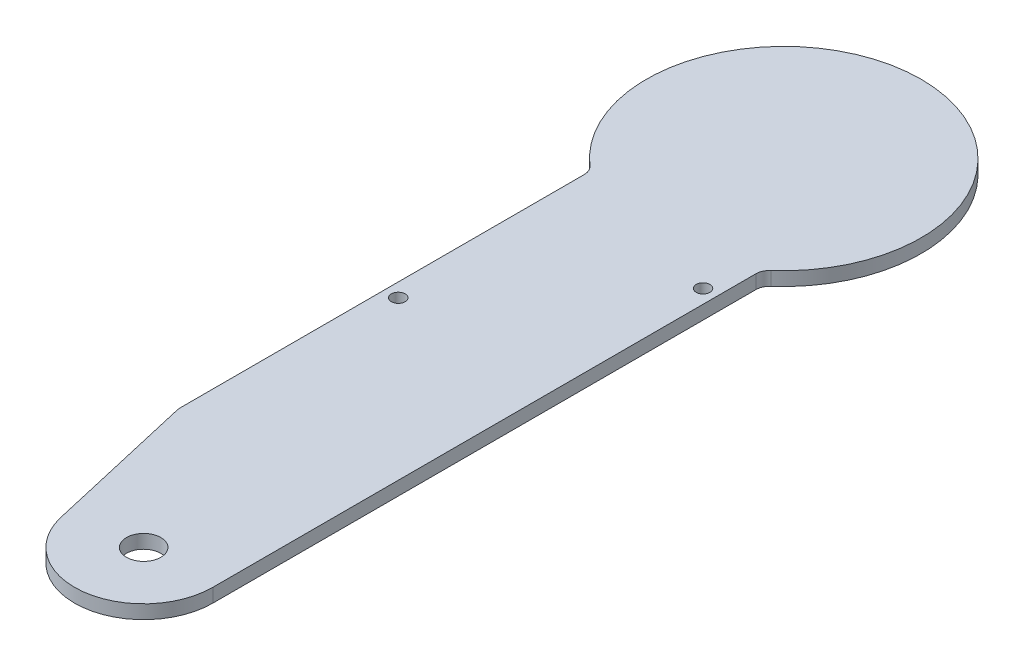
SolidWorks part; units mm, degrees
ref_plane "Front Plane" through (0, 0, 0) normal (0, 0, 1) x (1, 0, 0)
ref_plane "Top Plane" through (0, 0, 0) normal (0, 1, 0) x (1, 0, 0)
ref_plane "Right Plane" through (0, 0, 0) normal (1, 0, 0) x (0, 0, -1)
sketch "Sketch1" plane through (0, 0, 0) normal (0, 1, 0) x (1, 0, 0)
  line L0 (-15.875, -19.8279) -> (-15.875, -96.0279)
  line L1 (-15.875, -96.0279) -> (-9.3624, -124.2973)
  line L3 (15.875, -96.0279) -> (15.875, -19.8279)
  line L6 (-15.875, -19.8279) -> (15.875, -19.8279) construction
  line L7 (0, -19.8279) -> (0, 0) construction
  line L8 (-13.335, -57.9279) -> (-15.875, -57.9279) construction
  line L9 (13.335, -28.2506) -> (15.875, -28.2506) construction
  line L11 (15.875, -96.0279) -> (15.875, -121.4279)
  arc A0 (15.875, -19.8279) -> (-15.875, -19.8279) centre (0, 0) ccw
  arc A8 (-9.3624, -124.2973) -> (15.875, -121.4279) centre (3.0932, -121.4279) ccw
  circle A9 centre (3.0932, -121.4279) radius 3.175
  circle A10 centre (-13.335, -57.9279) radius 1.27
  circle A11 centre (13.335, -28.2506) radius 1.27
  dimension "D3" = 50.8
  dimension "D9" = 6.35
  dimension "D10" = 2.54
  dimension "D5" = 76.2
  dimension "D6" = 101.6
  dimension "D7" = 31.75
  dimension "D8" = 25.4
  dimension "D11" = 2.54
extrude "Boss-Extrude1" add sketch "Sketch1" along normal blind 2.54
fillet "Fillet1" radius 2.54 3 edges at (-15.875, 1.27, 96.0279) (-15.875, 1.27, 19.8279) (15.875, 1.27, 19.8279)
